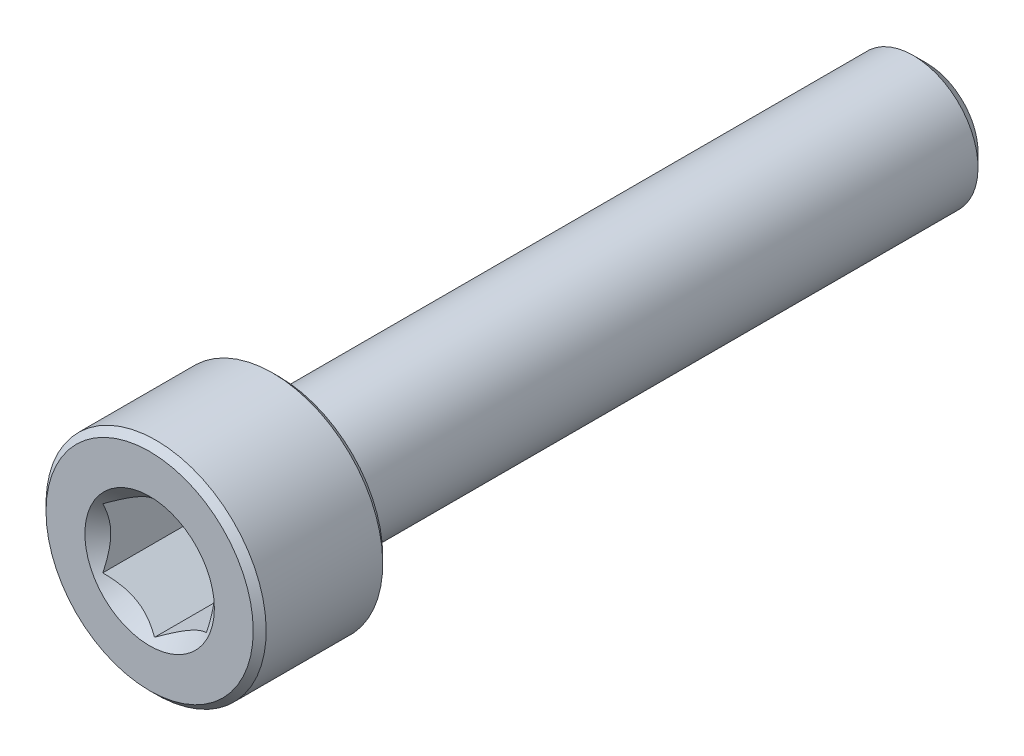
SolidWorks part; units mm, degrees
ref_plane "Front Plane" through (0, 0, 0) normal (0, 0, 1) x (1, 0, 0)
ref_plane "Top Plane" through (0, 0, 0) normal (0, 1, 0) x (1, 0, 0)
ref_plane "Right Plane" through (0, 0, 0) normal (1, 0, 0) x (0, 0, -1)
sketch "Sketch1" plane through (0, 0, 0) normal (1, 0, 0) x (0, 0, -1)
  line L0 (-15, 0) -> (15, 0) construction
  line L1 (15, 0) -> (15, 1.9804) construction
  line L2 (15, 1.9804) -> (14.4804, 2.5) construction
  line L3 (14.4804, 2.5) -> (14.4, 2.5) construction
  line L4 (14.4, 2.5) -> (-10, 2.5) construction
  line L5 (-10, 2.5) -> (-10, 4.25) construction
  line L6 (-10, 4.25) -> (-15, 4.25) construction
  line L7 (-15, 4.25) -> (-15, 0) construction
  line L8 (15, 1.9804) -> (15, 2.5) construction
  line L9 (14.95, 2.5866) -> (15.35, 1.8938) construction
  line L10 (15.35, 1.8938) -> (15.75, 2.5866) construction
  line L11 (15.75, 2.5866) -> (14.95, 2.5866) construction
  line L12 (15.35, 2.5866) -> (15.35, 2.5) construction
  line L13 (15.35, 1.8938) -> (15.35, 1.9804) construction
  line L14 (15.3, 1.9804) -> (15.4, 1.9804) construction
  line L15 (15, 2.5) -> (15.7, 2.5) construction
  line L16 (14.975, 2.5433) -> (15.725, 2.5433) construction
  line L17 (15, 0) -> (15, -2.5) construction
  line L18 (-10.25, 4.25) -> (-10, 4) construction
  line L19 (-14.75, 4.25) -> (-15, 4) construction
  line L20 (-10, 2.5) -> (-10, 0) construction
  line L21 (-10, 1.25) -> (-1.6667, 1.25) construction
  line L22 (-1.6667, 1.25) -> (6.6667, 1.25) construction
  line L23 (6.6667, 1.25) -> (15, 1.25) construction
  line L24 (-1.6667, 1.25) -> (-1.6667, 2.5) construction
  line L25 (-1.6667, 2.5) -> (-1.6667, 4.25) construction
  line L26 (6.6667, 1.25) -> (6.6667, 4.25) construction
  point P0 (-15, 2)
  point P3 (13, 2.5)
  point P4 (0, 0)
  point P18 (6.6667, 2.5)
  point P22 (15.35, 1.9804)
  point P24 (14.4, 2.5)
  point P25 (15.35, 2.5)
  point P28 (15.35, 2.5433)
  point P29 (13, -2.5)
  point P30 (-1.6667, 2.5)
  point P31 (-12.5, 4.25)
  point P37 (-10.875, 4.25)
  point P38 (-14.625, 4.25)
  point P45 (-1.6667, 1.25)
  point P46 (6.6667, 1.25)
  dimension "D2" = 0.1
  dimension "D7" = 0.25
  dimension "D8" = 0.25
  dimension "D9" = 0.25
  dimension "D10" = 0.125
  dimension "D11" = 0.625
  dimension "Drive Size" = 4
  dimension "Head Diameter" = 8.5
  dimension "Head Height" = 5
  dimension "Thread Pitch" = 0.8
  dimension "Thread Size" = 5
  dimension "Length" = 25
  dimension "D12" = 0.6
  dimension "D4" = 2
  dimension "D3" = 45
sketch "Sketch2" plane through (0, 0, 0) normal (1, 0, 0) x (0, 0, -1)
  line L0 (-15, 0) -> (-15, 4)
  line L1 (-14.75, 4.25) -> (-10.25, 4.25)
  line L2 (-10, 4) -> (-10, 2.75)
  line L4 (14.4804, 2.5) -> (15, 1.9804)
  line L5 (15, 1.9804) -> (15, 0)
  line L6 (-10, 4.25) -> (-15, 4.25) construction
  line L7 (15, 0) -> (-15, 0)
  line L8 (-14.75, 4.25) -> (-15, 4) construction
  line L10 (-14.75, 4.25) -> (-15, 4)
  line L14 (-10.25, 4.25) -> (-10, 4) construction
  line L16 (-10.25, 4.25) -> (-10, 4)
  line L17 (-10, 2.5) -> (-10, 4.25) construction
  line L19 (-9.75, 2.5) -> (14.4804, 2.5)
  line L20 (14.4, 2.5) -> (-10, 2.5) construction
  arc A1 (-10, 2.75) -> (-9.75, 2.5) centre (-9.75, 2.75) ccw
  dimension "D3" = 0.25
revolve "Revolve1" add sketch "Sketch2" angle 360 about L7
sketch "Sketch3" plane through (0, 0, 15) normal (0, 0, 1) x (1, 0, 0)
  line L1 (2, -1.1547) -> (2, 1.1547)
  line L2 (2, 1.1547) -> (0, 2.3094)
  line L3 (0, 2.3094) -> (-2, 1.1547)
  line L4 (-2, 1.1547) -> (-2, -1.1547)
  line L5 (-2, -1.1547) -> (0, -2.3094)
  line L6 (0, -2.3094) -> (2, -1.1547)
  circle A0 centre (0, 0) radius 2 construction
  circle A1 centre (0, 0) radius 4.25 construction
  circle A2 centre (0, 0) radius 4.25 construction
  circle A3 centre (0, 0) radius 2.3094 construction
  point P13 (0, 0)
extrude "Cut-Extrude1" cut sketch "Sketch3" against normal offset from surface (4 mm away) 1 up to face at (0, 4, 10)
sketch "Sketch4" plane through (0, 0, 15) normal (0, 0, 1) x (1, 0, 0)
  circle A0 centre (0, 0) radius 2.5
  dimension "D1" = 5
extrude "Cut-Extrude2" cut sketch "Sketch4" against normal up to vertex (2.5 mm away) draft 45 up to point (0, 4.25, 12.5)
sketch "Sketch11" plane through (0, 0, 0) normal (1, 0, 0) x (0, 0, -1)
  line L0 (-15, 0) -> (15, 0) construction
  line L1 (-15, 0) -> (15, 0) construction
  line L2 (-5.3125, 0) -> (-5.3125, 2.5) construction
  line L3 (14.4, 2.5) -> (-10, 2.5) construction
  line L4 (10.3125, 0) -> (10.3125, 2.5) construction
  line L6 (15, 1.9804) -> (15, 2.5) construction
  point P2 (-5.3125, 0)
  point P3 (10.3125, 0)
  dimension "D1" = 4.6875
  dimension "D2" = 4.6875
sketch "Sketch6" [suppressed] plane through (0, 0, -15) normal (0, 0, -1) x (-1, 0, 0)
  circle A0 centre (0, 0) radius 2.5
curve "Helix/Spiral1" [suppressed] pitch 0.8 height 25.8 turns 32.25
sketch "Sketch10" [suppressed] plane through (0, 0, 0) normal (1, 0, 0) x (0, 0, -1)
  line L0 (-9.75, -4.25) -> (-9.75, 4.25)
  line L5 (-15, 0) -> (15, 0) construction
  line L6 (-9.75, 2.5) -> (-9.75, -2.5) construction
  point P3 (-9.75, 0)
split "Split1" [suppressed] bodies to split 106
sketch "Sketch7" [suppressed] plane through (0, 0, 0) normal (1, 0, 0) x (0, 0, -1)
  line L0 (14.975, 2.5433) -> (15.725, 2.5433)
  line L1 (15.725, 2.5433) -> (15.4, 1.9804)
  line L2 (15.4, 1.9804) -> (15.3, 1.9804)
  line L3 (15.3, 1.9804) -> (14.975, 2.5433)
sweep "Cut-Sweep1" [suppressed] cut profiles "Sketch7" path "Helix/Spiral1"
sketch "Sketch8" [suppressed] plane through (0, 0, 0) normal (1, 0, 0) x (0, 0, -1)
  line L0 (-10, 0) -> (-10, 2.5)
  line L1 (-9.75, -2.5) -> (-9.75, 2.5) construction
  line L2 (-10, 2.5) -> (-9.75, 2.5)
  line L4 (-9.75, 2.5) -> (-8.3066, 0)
  line L5 (-8.3066, 0) -> (-10, 0)
  line L6 (14.4, 2.5) -> (-10, 2.5) construction
  line L7 (-15, 0) -> (15, 0) construction
  dimension "D1" = 60
revolve "Revolve2" [suppressed] add sketch "Sketch8" angle 360 about L5
ref_plane "Plane1" [suppressed] through (0, 0, 15) normal (0, 0, 1) x (1, 0, 0)
sketch "Sketch12" [suppressed] plane through (0, 0, 15) normal (0, 0, 1) x (1, 0, 0)
  line L0 (0, 0) -> (0.1483, 4.2474) construction
  line L1 (0, 0) -> (-0.1483, 4.2474) construction
  line L2 (0, 4.1437) -> (0, 4.3563) construction
  line L3 (-0.2572, 4.3563) -> (0.2572, 4.3563)
  line L4 (-0.2572, 4.3563) -> (-0.0762, 4.1753)
  line L5 (0.0762, 4.1753) -> (0.2572, 4.3563)
  circle A0 centre (0, 0) radius 4.25 construction
  arc A1 (-0.0762, 4.1753) -> (0.0762, 4.1753) centre (0, 4.2516) ccw
  point P9 (0, 4.3563)
  point P13 (0, 4.25)
  dimension "D1" = 4
  dimension "D2" = 0.1063
extrude "Cut-Extrude3" [suppressed] cut sketch "Sketch12" against normal blind 4
pattern_circular "CirPattern1" [suppressed] count 72 over 360 about axis through (0, 0, 15) along (0, 0, -1) of bodies 118
equation "\"D2@Sketch1\" = \"Thread Pitch@Sketch1\" / 8"
equation "\"D4@Helix/Spiral1\" = \"Thread Pitch@Sketch1\""
equation "\"D7@Sketch1\" = \"Head Height@Sketch1\" * .05"
equation "\"D8@Sketch1\"=\"D7@Sketch1\""
equation "\"D9@Sketch1\"=\"D7@Sketch1\""
equation "\"D10@Sketch1\"=\"D7@Sketch1\"/2"
equation "\"D11@Sketch1\"=\"D10@Sketch1\"*5"
equation "\"D4@Sketch1\"=\"Thread Pitch@Sketch1\"*2.5"
equation "\"D12@Sketch1\"=\"Thread Pitch@Sketch1\"*.75"
equation "\"D3@Helix/Spiral1\"=\"Length@Sketch1\"+\"Thread Pitch@Sketch1\""
equation "\"D3@Sketch2\" = \"Thread Size@Sketch1\" * 0.05"
equation "\"D1@Sketch11\"=\"Length@Sketch1\"*0.1875"
equation "\"D2@Sketch11\"=\"D1@Sketch11\""
equation "\"D2@Sketch12\"=\"Head Diameter@Sketch1\"*.0125"
equation "\"D1@Cut-Extrude3\"=\"Head Height@Sketch1\"*.8"
equation "\"D1@CirPattern1\"=\"D3@CirPattern1\"/(1.25*\"D1@Sketch12\")"
equation "\"D1@Sketch4\"=\"Drive Size@Sketch1\"*1.25"
